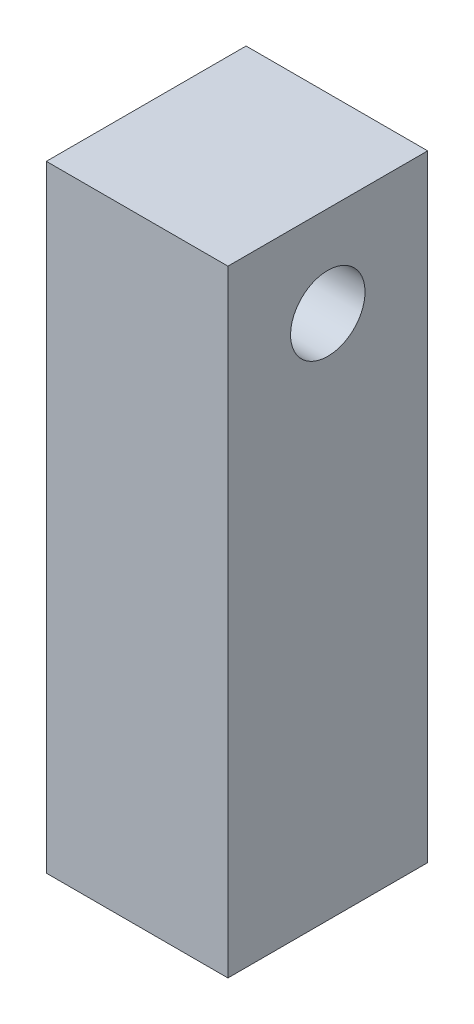
SolidWorks part; units mm, degrees
ref_plane "Front Plane" through (0, 0, 0) normal (0, 0, 1) x (1, 0, 0)
ref_plane "Top Plane" through (0, 0, 0) normal (0, 1, 0) x (1, 0, 0)
ref_plane "Right Plane" through (0, 0, 0) normal (1, 0, 0) x (0, 0, -1)
sketch "Sketch1" plane through (0, 0, 0) normal (0, 0, 1) x (1, 0, 0)
  line L1 (-25, 0) -> (25, 0)
  line L2 (-25, 0) -> (-25, -150)
  line L3 (-25, -150) -> (25, -150)
  line L4 (25, 0) -> (25, -150)
  dimension "D1" = 50
  dimension "D2" = 150
extrude "Boss-Extrude1" add sketch "Sketch1" against normal blind 55
sketch "Sketch2" plane through (25, 0, 0) normal (1, 0, 0) x (0, 0, -1)
  line L0 (55, 0) -> (0, 0) construction
  line L1 (0, -150) -> (0, 0) construction
  circle A0 centre (27.5, -25) radius 10.25
  dimension "D1" = 25
  dimension "D2" = 27.5
extrude "Cut-Extrude1" cut sketch "Sketch2" against normal blind 45 and the other way through all
sketch "Sketch7" plane through (-20, 0, 0) normal (1, 0, 0) x (0, 0, -1)
  line L0 (27.5, -17) -> (27.5, -33) construction
  circle A0 centre (27.5, -25) radius 8
  circle A1 centre (27.5, -17) radius 1
  circle A2 centre (35.5, -25) radius 1
  circle A3 centre (27.5, -33) radius 1
  circle A4 centre (19.5, -25) radius 1
  circle A5 centre (27.5, -25) radius 4.25
  point P14 (27.5, -25)
  dimension "D1" = 16
  dimension "D2" = 2
  dimension "D4" = 8.5
  dimension "D3" = 4
extrude "Cut-Extrude3" cut sketch "Sketch7" against normal blind 10 contours L0 A0 A1 | A0 A1 | A0 L0 A1 | A0 A4 | A0 A4 | L0 A3 A0 | A3 L0 A0 | A0 A3 | A0 A2 | A0 A2 | A5 L0 | L0 A5 region at (-20, -17.4355, -27.9155) region at (-20, -16.587, -27.5) region at (-20, -17.4355, -27.0845) region at (-20, -25, -29.3038) region at (-20, -25, -25.6962) region at (-20, -25, -35.913) region at (-20, -25, -35.0645) region at (-20, -25, -19.9355) region at (-20, -25, -19.087) region at (-20, -32.5645, -27.9155) region at (-20, -32.5645, -27.0845) region at (-20, -33.413, -27.5)
sketch "Sketch8" plane through (25, 0, 0) normal (1, 0, 0) x (0, 0, -1)
  line L1 (55, -150) -> (55, 0) construction
  line L3 (0, -150) -> (55, -150)
  line L4 (0, -150) -> (0, -205)
  line L5 (0, -205) -> (55, -205)
  line L6 (55, -150) -> (55, -205)
  circle A1 centre (27.5, -180) radius 10.25
  circle A3 centre (27.5, -25) radius 10.25 construction
  dimension "D1" = 27.5
  dimension "D2" = 155
  dimension "D3" = 25
extrude "Boss-Extrude2" add sketch "Sketch8" against normal blind 50
sketch "Sketch10" plane through (0, 0, 0) normal (0, 0, 1) x (1, 0, 0)
  line L0 (-25, -205) -> (25, -205) construction
  line L5 (17, -205) -> (-17, -205)
  line L6 (17, -205) -> (17, -144.75)
  line L8 (-17, -205) -> (-17, -144.75)
  line L9 (-25, 0) -> (-25, -205) construction
  line L10 (-25, -180) -> (25, -180)
  line L13 (25, -169.75) -> (-25, -169.75)
  line L14 (25, -169.75) -> (25, -190.25)
  line L15 (25, -190.25) -> (-25, -190.25)
  line L16 (-25, -169.75) -> (-25, -190.25)
  line L17 (25, -205) -> (25, 0) construction
  line L18 (0, -180) -> (17, -180)
  line L19 (0, -180) -> (0, -191.25)
  line L20 (0, -191.25) -> (17, -191.25)
  line L21 (17, -180) -> (17, -191.25)
  line L22 (17, -191.25) -> (-17, -191.25)
  line L23 (17, -191.25) -> (17, -169.75)
  line L24 (17, -169.75) -> (-17, -169.75)
  line L25 (-17, -191.25) -> (-17, -169.75)
  line L26 (17, -191.25) -> (-17, -191.25)
  line L27 (17, -191.25) -> (17, -144.75)
  line L28 (17, -144.75) -> (-17, -144.75)
  line L29 (-17, -191.25) -> (-17, -144.75)
  line L30 (-25, -169.75) -> (-17, -169.75)
  line L31 (-25, -169.75) -> (-25, -205)
  line L32 (-25, -205) -> (-17, -205)
  line L33 (-17, -169.75) -> (-17, -205)
  line L34 (25, -169.75) -> (17, -169.75)
  line L35 (25, -169.75) -> (25, -205)
  line L36 (25, -205) -> (17, -205)
  line L37 (17, -169.75) -> (17, -205)
  line L38 (-25, -169.75) -> (25, -169.75)
  line L39 (-25, -169.75) -> (-25, -164.75)
  line L40 (-25, -164.75) -> (25, -164.75)
  line L41 (25, -169.75) -> (25, -164.75)
  line M7 (-25, 0) -> (-25, -205)
  line M8 (-25, -205) -> (25, -205)
  line M9 (25, -205) -> (25, 0)
  dimension "D1" = 8
  dimension "D2" = 8
  dimension "D3" = 11.25
  dimension "D4" = 46.5
  dimension "D5" = 60.25
  dimension "D6" = 5
extrude "Cut-Extrude4" cut sketch "Sketch10" against normal through all contours L20 L22 L8 L6 M8 | L8 L15 M7 M8 | L15 L6 M9 M8 | L15 L8 L10 M7 | L8 L13 L10 M7 | L13 L6 L10 M9 | L15 L10 L6 M9 | L19 L10 L8 L15 | L10 L19 L15 L6 | L6 L13 L8 L10 | L22 L19 L15 L8 | L19 L20 L6 L15 | L29 L40 L27 L28 | L40 L8 L13 L6 region at (0, -198.125, 0) region at (21, -197.625, 0) region at (-21, -197.625, 0) region at (8.5, -190.75, 0) region at (-8.5, -190.75, 0) region at (8.5, -185.125, 0) region at (21, -185.125, 0) region at (-21, -185.125, 0) region at (-8.5, -185.125, 0) region at (0, -174.875, 0) region at (21, -174.875, 0) region at (-21, -174.875, 0) region at (0, -167.25, 0) region at (0, -154.75, 0)
sketch "Sketch11" plane through (0, -144.75, 0) normal (0, -1, 0) x (1, 0, 0)
  line L0 (17, -55) -> (17, 0) construction
  line L1 (-17, 0) -> (17, 0)
  line L2 (-17, 0) -> (-17, -13.25)
  line L3 (-17, -13.25) -> (17, -13.25)
  line L4 (17, 0) -> (17, -13.25)
  line L5 (25, -27.5) -> (-30.9131, -27.5) construction
  line L6 (25, -55) -> (25, 0) construction
  line L7 (17, -55) -> (17, -41.75)
  line L8 (-17, -41.75) -> (17, -41.75)
  line L9 (-17, -55) -> (-17, -41.75)
  line L10 (-17, -55) -> (17, -55)
  dimension "D1" = 14.25
extrude "Boss-Extrude4" add sketch "Sketch11" along normal blind 25
sketch "Sketch12" plane through (25, 0, 0) normal (1, 0, 0) x (0, 0, -1)
  circle A0 centre (27.6629, -180) radius 13.0911
  circle A1 centre (27.5, -25) radius 10.25 construction
  dimension "D1" = 155
